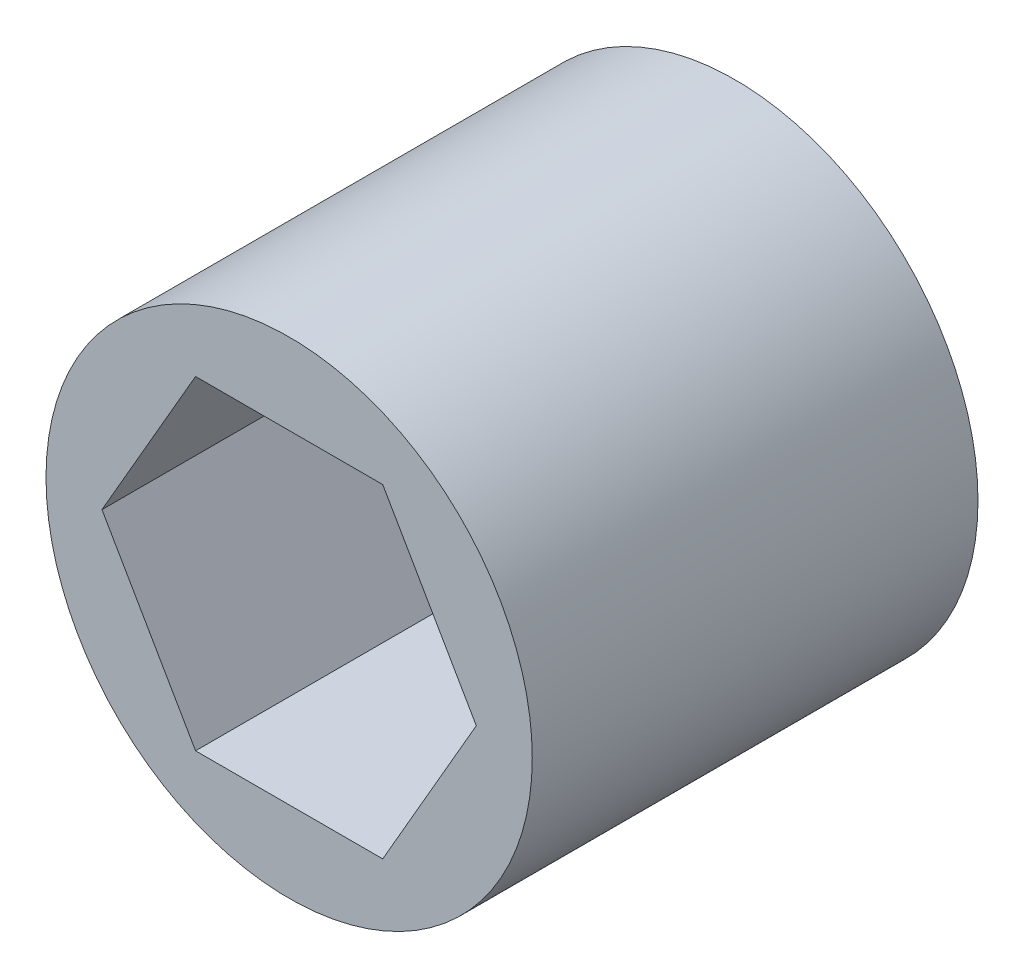
SolidWorks part; units mm, degrees
material "Nylon 101"
ref_plane "Front Plane" through (0, 0, 0) normal (0, 0, 1) x (1, 0, 0)
ref_plane "Top Plane" through (0, 0, 0) normal (0, 1, 0) x (1, 0, 0)
ref_plane "Right Plane" through (0, 0, 0) normal (1, 0, 0) x (0, 0, -1)
sketch "Sketch1" plane through (0, 0, 0) normal (0, 0, 1) x (1, 0, 0)
  line L1 (-3.6662, 6.35) -> (-7.3323, 0)
  line L2 (-7.3323, 0) -> (-3.6662, -6.35)
  line L3 (-3.6662, -6.35) -> (3.6662, -6.35)
  line L4 (3.6662, -6.35) -> (7.3323, 0)
  line L5 (7.3323, 0) -> (3.6662, 6.35)
  line L6 (3.6662, 6.35) -> (-3.6662, 6.35)
  circle A0 centre (0, 0) radius 6.35 construction
  circle A1 centre (0, 0) radius 9.525
  point P10 (0, 6.35)
  dimension "D1" = 12.7
  dimension "D2" = 19.05
extrude "Boss-Extrude1" add sketch "Sketch1" along normal blind 17.4625
